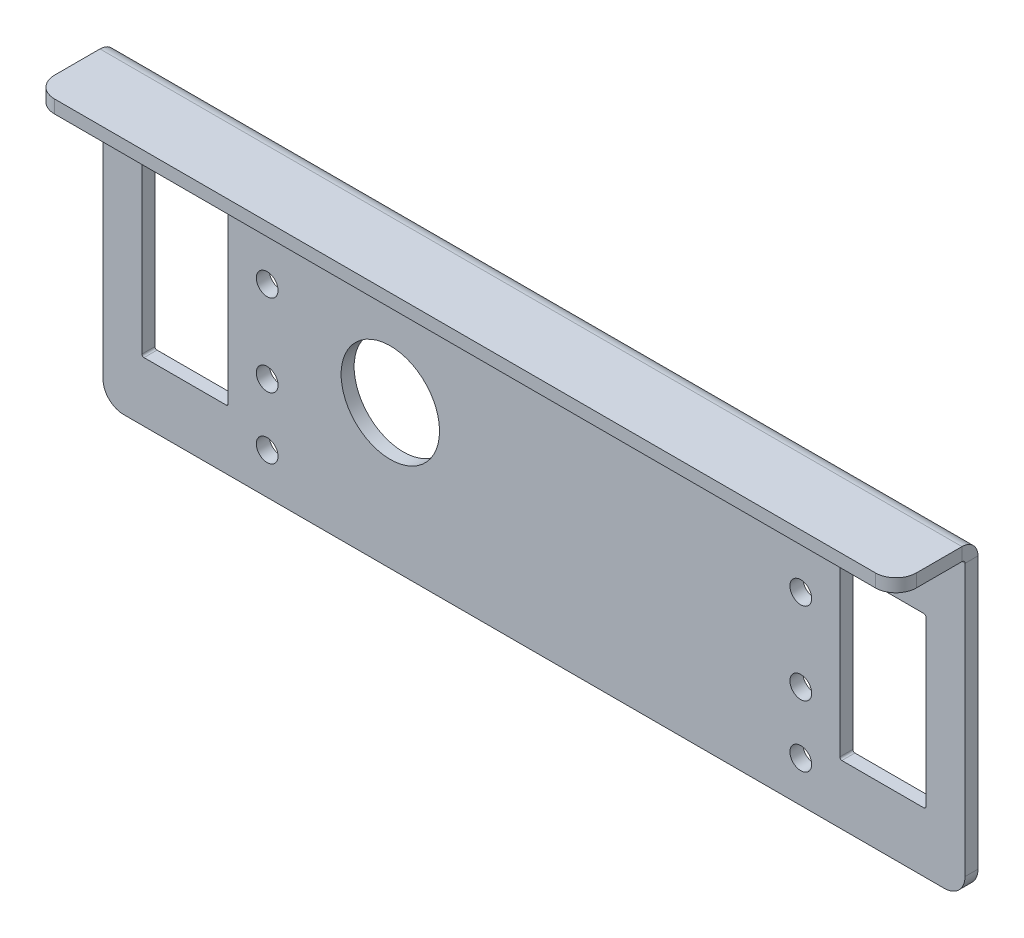
SolidWorks part; units mm, degrees
note: The reader was unsure of these and kept them because the rebuilt part matched: flange length of "Edge-Flange1".
material "5052-H32"
ref_plane "Front Plane" through (0, 0, 0) normal (0, 0, 1) x (1, 0, 0)
ref_plane "Top Plane" through (0, 0, 0) normal (0, 1, 0) x (1, 0, 0)
ref_plane "Right Plane" through (0, 0, 0) normal (1, 0, 0) x (0, 0, -1)
sketch "Sketch1" plane through (0, 0, 0) normal (0, 0, 1) x (1, 0, 0)
  line L0 (-30, 25) -> (100, 25) construction
  line L1 (-70, 40) -> (140, 40)
  line L2 (-70, 40) -> (-70, -35)
  line L3 (-70, -35) -> (140, -35)
  line L4 (140, 40) -> (140, -35)
  line L5 (-30, 25) -> (-30, -25) construction
  line L6 (35.3553, -35.3553) -> (0, 0) construction
  line L7 (-50, 10) -> (120, 10) construction
  line L8 (-50, 10) -> (-50, -10) construction
  line L9 (-50, -10) -> (120, -10) construction
  line L10 (120, 10) -> (120, -10) construction
  line L11 (0, 0) -> (50, 0) construction
  line L13 (-60.5, 20.5) -> (-39.5, 20.5)
  line L14 (-60.5, 20.5) -> (-60.5, -20.5)
  line L15 (-60.5, -20.5) -> (-39.5, -20.5)
  line L16 (-39.5, 20.5) -> (-39.5, -20.5)
  line L17 (109.5, 20.5) -> (130.5, 20.5)
  line L18 (109.5, 20.5) -> (109.5, -20.5)
  line L19 (109.5, -20.5) -> (130.5, -20.5)
  line L20 (130.5, 20.5) -> (130.5, -20.5)
  circle A0 centre (0, 0) radius 11.9875
  circle A1 centre (-30, 25) radius 2.5 construction
  circle A2 centre (100, 25) radius 2.5 construction
  circle A3 centre (-30, -25) radius 2.5 construction
  circle A4 centre (100, -25) radius 2.5 construction
  circle A5 centre (-50, 10) radius 3 construction
  circle A6 centre (-50, -10) radius 3 construction
  circle A7 centre (120, -10) radius 3 construction
  circle A8 centre (120, 10) radius 3 construction
  circle A9 centre (50, 0) radius 40 construction
  arc A10 (50, 0) -> (35.3553, -35.3553) centre (0, 0) cw construction
  circle A11 centre (35.3553, -35.3553) radius 40 construction
  circle A12 centre (-30, 10) radius 2.5 construction
  circle A13 centre (-30, -10) radius 2.5 construction
  circle A14 centre (100, 10) radius 2.5 construction
  circle A15 centre (100, -10) radius 2.5 construction
  point P20 (-50, 0)
  point P28 (-30, 0)
  point P32 (35, 40)
  point P34 (35, 10)
  point P41 (-50, 20.5)
  point P42 (-39.5, 0)
  point P43 (120, 20.5)
  dimension "D1" = 23.975
  dimension "D6" = 50
  dimension "D7" = 5
  dimension "D2" = 6
  dimension "D9" = 20
  dimension "D11" = 80
  dimension "D12" = 50
  dimension "D17" = 5
  dimension "D18" = 20
  dimension "D19" = 20
  dimension "D20" = 10
  dimension "D3" = 20
  dimension "D4" = 130
  dimension "D5" = 15
  dimension "D8" = 30
  dimension "D10" = 20
  dimension "D13" = 45
  dimension "D14" = 20
  dimension "D15" = 21
  dimension "D16" = 41
base flange "Base-Flange1" sketch "Sketch1" thickness 3.175 reverse thickness direction no parameters "D1"=0.7366
edge flange "Edge-Flange1" sketch "Sketch8" flange angle 90 flange length 20 flange position material inside bend radius 0.7366 thickness 3.175 relief rectangular parameters "D6"=10
sketch "Sketch8" plane through (0, 40, 0) normal (0, -1, 0) x (1, 0, 0)
  line L2 (-70, 0) -> (-70, 16.825)
  line L3 (-70, 16.825) -> (140, 16.825)
  line L4 (140, 16.825) -> (140, 0)
  line L9 (140, 0) -> (-70, 0) construction
  line L10 (140, 0) -> (-70, 0)
bend "EdgeBend1" bend radius 0.7366 bend angle 90 parameters "D5"=1
hole_wizard "M5 Clearance Hole1" positions "3DSketch1" profile "Sketch9" hole size "M5" standard "ANSI Metric" end condition up to next
sketch3d "3DSketch1"
  point P0 (-30, 25, 0)
  point P2 (-30, -25, 0)
  point P4 (100, -25, 0)
  point P6 (100, 25, 0)
  point P18 (-30, 10, 0)
  point P20 (-30, -10, 0)
  point P22 (100, -10, 0)
  point P24 (100, 10, 0)
  point P27 (95, 10, 0)
  point P29 (95, -10, 0)
  point P31 (-25, -10, 0)
  point P33 (-25, 10, 0)
sketch "Sketch9" plane through (-30, 25, 0) normal (1, 0, 0) x (0, -1, 0)
  line L0 (0, 0) -> (0, 3.175)
  line L1 (0, 3.175) -> (2.65, 3.175)
  line L2 (2.65, 3.175) -> (2.65, 0)
  line L5 (2.65, 0) -> (0, 0)
  line L11 (0, -6.35) -> (0, 107.95) construction
  dimension "Thru Hole Dia." = 5.3
  dimension "Thru Hole Depth" = 3.175
fillet "Fillet1" radius 5 4 edges at (140, -35, -1.5875) (140, 38.4125, 16.825) (-70, 38.4125, 16.825) (-70, -35, -1.5875)
fillet "Fillet2" radius 0.5 8 edges at (109.5, -20.5, -1.5875) (109.5, 20.5, -1.5875) (130.5, 20.5, -1.5875) (130.5, -20.5, -1.5875) (-39.5, -20.5, -1.5875) (-39.5, 20.5, -1.5875) (-60.5, 20.5, -1.5875) (-60.5, -20.5, -1.5875)
sketch "Bend-Lines1" [suppressed] plane through (0, 0, 0) normal (0, 1, 0) x (1, 0, 0)
sketch "Bounding-Box1" [suppressed] plane through (0, 0, 0) normal (0, 1, 0) x (1, 0, 0)
sheet metal parameters "Sheet-Metal4" thickness 3.175 parameters "D1"=0.7366
flat pattern "Flat-Pattern4" [suppressed]
sketch "Bend-Lines2" plane through (0, 0, 0) normal (0, 1, 0) x (1, 0, 0)
sketch3d "Bounding-Box2" [suppressed]
  line L0 (70, -40, 0) -> (-140, -40, 0) construction
  line L1 (70, 40, 0) -> (-140, 40, 0) construction
  line L2 (70, -40, 0) -> (70, 40, 0) construction
  line L3 (-140, -40, 0) -> (-140, 40, 0) construction
sheet metal parameters "Sheet-Metal5" thickness 3.175 parameters "D1"=0.7366
flat pattern "Flat-Pattern4"
sketch "Bend-Lines2" plane through (0, 0, 0) normal (0, 0, 1) x (1, 0, 0)
  line L0 (140, 37.9137) -> (-70, 37.9137) construction
  line L1 (140, 37.9137) -> (-70, 37.9137) construction
sketch3d "Bounding-Box2" [suppressed]
  line L0 (-70, -40, 0) -> (140, -40, 0) construction
  line L1 (-70, 55.8275, 0) -> (140, 55.8275, 0) construction
  line L2 (-70, -40, 0) -> (-70, 55.8275, 0) construction
  line L3 (140, -40, 0) -> (140, 55.8275, 0) construction
bend of the flat pattern "Flatten-<EdgeBend1>1"
sheet metal parameters "Sheet-Metal6" thickness 3.175 parameters "D1"=0.7366
flat pattern "Flat-Pattern4"
sketch "Bend-Lines2" plane through (0, 0, 0) normal (0, 0, 1) x (1, 0, 0)
  line L0 (140, 37.9137) -> (-70, 37.9137) construction
  line L1 (140, 37.9137) -> (-70, 37.9137) construction
sketch3d "Bounding-Box2" [suppressed]
  line L0 (-70, 55.8275, 0) -> (140, 55.8275, 0) construction
  line L1 (-70, -35, 0) -> (140, -35, 0) construction
  line L2 (-70, 55.8275, 0) -> (-70, -35, 0) construction
  line L3 (140, 55.8275, 0) -> (140, -35, 0) construction
bend of the flat pattern "Flatten-<EdgeBend1>1"
